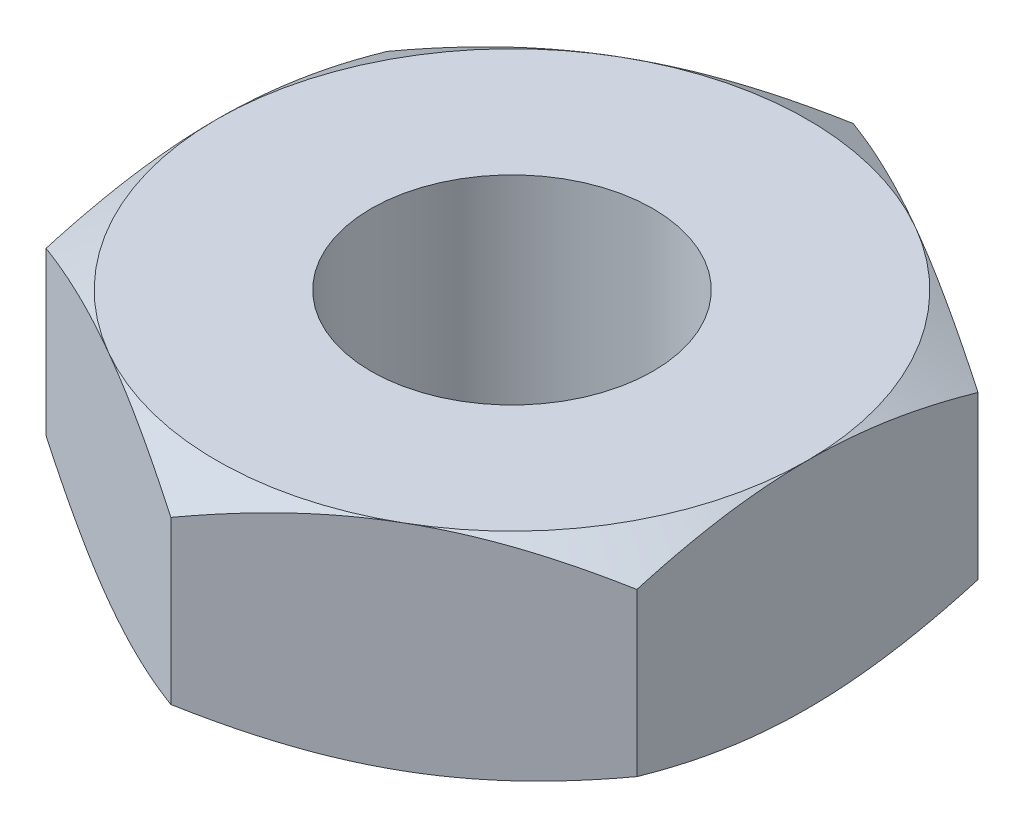
SolidWorks part; units mm, degrees
material "Alloy Steel (SS)"
ref_plane "Front Plane" through (0, 0, 0) normal (0, 0, 1) x (1, 0, 0)
ref_plane "Top Plane" through (0, 0, 0) normal (0, 1, 0) x (1, 0, 0)
ref_plane "Right Plane" through (0, 0, 0) normal (1, 0, 0) x (0, 0, -1)
sketch "Sketch1" plane through (0, 0, 0) normal (0, 1, 0) x (1, 0, 0)
  line L1 (-4.3656, 2.5205) -> (-4.3656, -2.5205)
  line L2 (-4.3656, -2.5205) -> (0, -5.041)
  line L3 (0, -5.041) -> (4.3656, -2.5205)
  line L4 (4.3656, -2.5205) -> (4.3656, 2.5205)
  line L5 (4.3656, 2.5205) -> (0, 5.041)
  line L6 (0, 5.041) -> (-4.3656, 2.5205)
  circle A0 centre (0, 0) radius 4.3656 construction
  circle A1 centre (0, 0) radius 2.0828
  dimension "Thread Size" = 4.1656
  dimension "Hex" = 8.7312
extrude "Boss-Extrude1" add sketch "Sketch1" along normal mid plane 3.175
sketch "Sketch2" plane through (0, 1.5875, 0) normal (0, 1, 0) x (1, 0, 0)
  circle A0 centre (0, 0) radius 2.0828 construction
  circle A1 centre (0, 0) radius 2.0828
curve "Helix/Spiral1" [suppressed] pitch 0.7937 height 3.9688 turns 5 parameters "Pitch"=0.7937
sketch "Sketch3" plane through (0, 0, 0) normal (1, 0, 0) x (0, 0, -1)
  line L0 (1.5672, 1.9844) -> (2.0828, 2.282)
  line L1 (2.0828, 2.282) -> (2.0828, 1.5875)
  line L2 (2.0828, 1.5875) -> (1.5672, 1.8852)
  line L3 (1.5672, 1.8852) -> (1.5672, 1.9844)
  line L4 (1.825, 2.1332) -> (1.825, 1.7363) construction
  line L5 (1.5672, 1.9348) -> (2.0828, 1.9348) construction
  line L6 (2.0828, 1.5875) -> (-2.0828, 1.5875) construction
  dimension "D1" = 60
  dimension "D2" = 0.0992
  dimension "D3" = 0.3969
sweep "Sweep1" [suppressed] add profiles "Sketch3" path "Helix/Spiral1"
sketch "Sketch4" plane through (0, 1.5875, 0) normal (0, 1, 0) x (1, 0, 0)
  circle A1 centre (0, 0) radius 2.0828
  circle A2 centre (0, 0) radius 2.0828
  dimension "D1" = 0
extrude "Cut-Extrude1" [suppressed] cut sketch "Sketch4" along normal through all and the other way through all draft 45
sketch "Sketch5" plane through (0, 1.5875, 0) normal (0, 1, 0) x (1, 0, 0)
  circle A0 centre (0, 0) radius 4.3656 construction
  circle A1 centre (0, 0) radius 4.3656
extrude "Cut-Extrude2" cut sketch "Sketch5" against normal through all draft 60 flip side to cut
mirror "Mirror1" about plane through (0, 0, 0) normal (0, 1, 0) of "Cut-Extrude2", "Cut-Extrude1"
equation "\"D2@Sketch3\" = \"Pitch@Helix/Spiral1\"*.125"
equation "\"D3@Sketch3\" = \"Pitch@Helix/Spiral1\"*.5"
equation "\"D3@Helix/Spiral1\" = \"Height@Boss-Extrude1\"+\"Pitch@Helix/Spiral1\""
